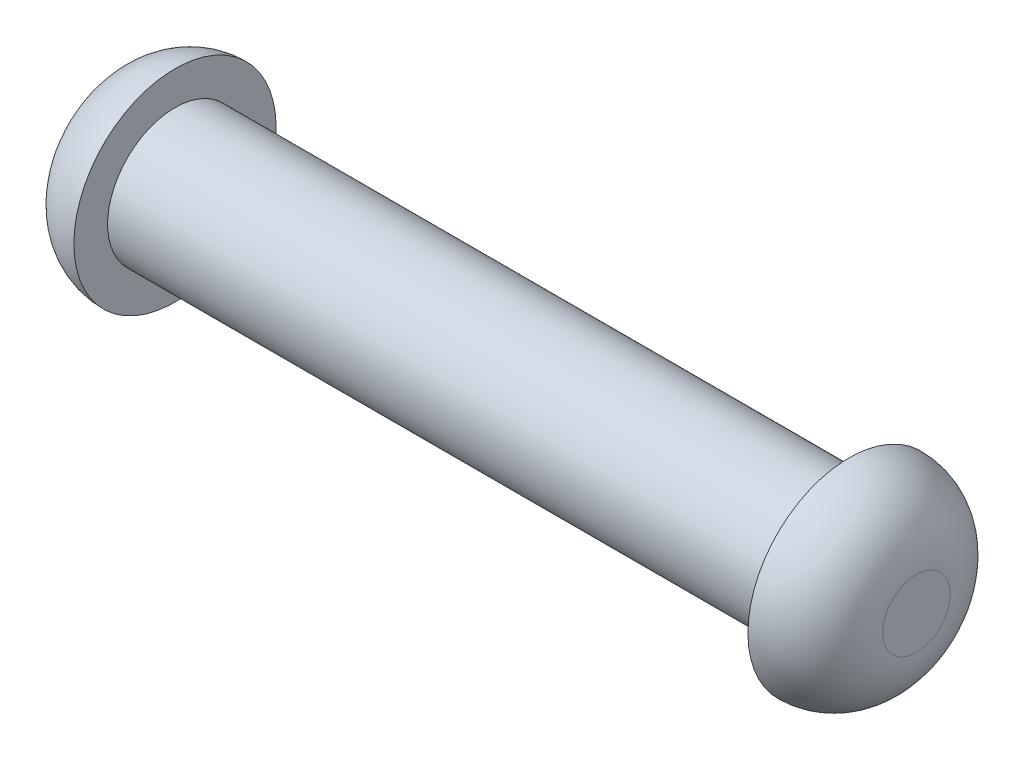
SolidWorks part; units mm, degrees
material "AISI 304"
ref_plane "Front Plane" through (0, 0, 0) normal (0, 0, 1) x (1, 0, 0)
ref_plane "Top Plane" through (0, 0, 0) normal (0, 1, 0) x (1, 0, 0)
ref_plane "Right Plane" through (0, 0, 0) normal (1, 0, 0) x (0, 0, -1)
sketch "Sketch2" plane through (0, 0, 0) normal (0, 0, 1) x (1, 0, 0)
  line L5 (1, 1) -> (11, 1)
  line L6 (11, 1) -> (11, 1.5)
  line L7 (11, 1.5) -> (12, 1.5)
  line L8 (12, 1.5) -> (12, 0)
  line L9 (12, 0) -> (0, 0)
  line L10 (1, 1) -> (1, 1.5)
  line L11 (1, 1.5) -> (0, 1.5)
  line L12 (0, 1.5) -> (0, 0)
  dimension "D1" = 10
  dimension "D2" = 1
  dimension "D3" = 1
  dimension "D4" = 1
  dimension "D5" = 1.5
  dimension "D7" = 1.5
revolve "Revolve1" add sketch "Sketch2" angle 360 about L9
fillet "Fillet1" radius 1 2 edges at (12, 0, -1.5) (0, 0, -1.5)
